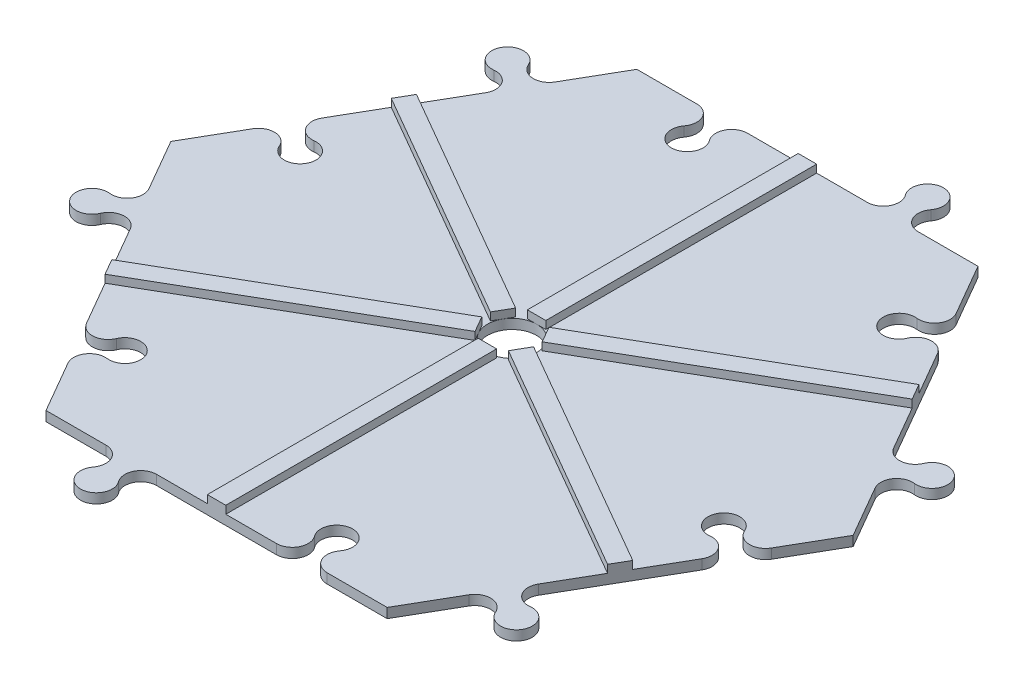
SolidWorks part; units mm, degrees
ref_plane "Front Plane" through (0, 0, 0) normal (0, 0, 1) x (1, 0, 0)
ref_plane "Top Plane" through (0, 0, 0) normal (0, 1, 0) x (1, 0, 0)
ref_plane "Right Plane" through (0, 0, 0) normal (1, 0, 0) x (0, 0, -1)
sketch "Sketch1" plane through (0, 0, 0) normal (0, 1, 0) x (1, 0, 0)
  line L10 (55.5, -96.1288) -> (111, 0)
  line L11 (111, 0) -> (55.5, 96.1288)
  line L12 (55.5, 96.1288) -> (-55.5, 96.1288)
  line L13 (-55.5, 96.1288) -> (-111, 0)
  line L14 (-111, 0) -> (-55.5, -96.1288)
  line L15 (-55.5, -96.1288) -> (55.5, -96.1288)
  circle A3 centre (0, 0) radius 96.1288 construction
  dimension "D1" = 111
extrude "Boss-Extrude1" add sketch "Sketch1" along normal blind 3.175 contours L14 L15 L10 L11 L12 L13
sketch "Sketch2" plane through (0, 0, 0) normal (0, 1, 0) x (1, 0, 0)
  line L0 (-19.495, 96.1288) -> (-36.005, 96.1288)
  line L1 (0, 0) -> (0, 96.1288) construction
  line L2 (0, 96.1288) -> (55.5, 96.1288) construction
  line L4 (27.75, 96.1288) -> (27.75, 118.9888) construction
  line L5 (19.495, 96.1288) -> (36.005, 96.1288)
  line L7 (55.5, 96.1288) -> (-55.5, 96.1288) construction
  arc A0 (-31.8775, 104.3838) -> (-27.75, 112.6388) centre (-27.75, 107.4794) cw construction
  arc A1 (-23.6225, 104.3838) -> (-27.75, 112.6388) centre (-27.75, 107.4794) ccw construction
  arc A2 (-19.495, 96.1288) -> (-23.6225, 104.3838) centre (-19.495, 101.2882) cw construction
  arc A3 (19.495, 96.1288) -> (23.6225, 104.3838) centre (19.495, 101.2882) ccw
  arc A4 (-36.005, 96.1288) -> (-31.8775, 104.3838) centre (-36.005, 101.2882) ccw construction
  arc A5 (23.6225, 104.3838) -> (27.75, 112.6388) centre (27.75, 107.4794) cw
  arc A7 (36.005, 96.1288) -> (31.8775, 104.3838) centre (36.005, 101.2882) cw
  arc A8 (31.8775, 104.3838) -> (27.75, 112.6388) centre (27.75, 107.4794) ccw
  arc A9 (-19.495, 96.1288) -> (-23.6225, 87.8738) centre (-19.495, 90.9694) ccw
  arc A10 (-23.6225, 87.8738) -> (-27.75, 79.6188) centre (-27.75, 84.7782) cw
  arc A11 (-31.8775, 87.8738) -> (-27.75, 79.6188) centre (-27.75, 84.7782) ccw
  arc A12 (-36.005, 96.1288) -> (-31.8775, 87.8738) centre (-36.005, 90.9694) cw
  dimension "D1" = 22.86
  dimension "D3" = 16.51
  dimension "D4" = 16.51
extrude "Boss-Extrude2" add sketch "Sketch2" along normal up to surface (3.175 mm away) contours A7 A8 A5 A3 L5 up to face at (0, 3.175, 0)
extrude "Cut-Extrude2" cut sketch "Sketch2<3>" along normal through all contours A11 A10 A9 L0 A12
sketch "Sketch2<3>" plane through (0, 0, 0) normal (0, 1, 0) x (1, 0, 0) same geometry as "Sketch2"
sketch "Sketch3" [suppressed] plane through (0, 0, 0) normal (0, 0, 1) x (1, 0, 0)
  line L0 (0, 0) -> (0, 25.4) construction
  dimension "D1" = 25.4
pattern_circular "CirPattern1" count 6 over 360 about axis through (0, 0, 0) along (0, 1, 0) of "Boss-Extrude2", "Cut-Extrude2" reverse direction yes
sketch "Sketch4" plane through (0, 3.175, 0) normal (0, 1, 0) x (1, 0, 0)
  circle A0 centre (0, 0) radius 8.001
  dimension "D1" = 16.002
extrude "Cut-Extrude3" cut sketch "Sketch4" against normal up to surface (3.175 mm away) up to face at (0, 0, 0)
sketch "Sketch5" plane through (0, 3.175, 0) normal (0, 1, 0) x (1, 0, 0)
  line L0 (-84.75, -45.4663) -> (-7.9236, -1.1106)
  line L1 (-81.75, -50.6625) -> (-4.9236, -6.3067)
  line L2 (-92.9975, -31.1812) -> (-73.5025, -64.9476) construction
  line L3 (-83.25, -48.0644) -> (-6.9291, -4.0005) construction
  line L4 (-7.9236, -1.1106) -> (-4.9236, -6.3067)
  line L5 (-92.9975, -31.1812) -> (-73.5025, -64.9476) construction
  line L6 (-84.75, -45.4663) -> (-81.75, -50.6625)
  line L7 (-5.4291, -6.5986) -> (-8.4291, -1.4024)
  circle A0 centre (0, 0) radius 8.001 construction
  arc A1 (-7.9236, -1.1106) -> (-4.9236, -6.3067) centre (0, 0) ccw
  dimension "D1" = 6
extrude "Boss-Extrude3" add sketch "Sketch5" along normal blind 2.54 contours L6 L3 L7 L0 | L3 L6 L1 L7 region at (-45.8395, 3.175, 24.7334) region at (-44.3395, 3.175, 27.3315)
pattern_circular "CirPattern2" count 6 over 360 about axis through (0, -22.6302, 0) along (0, 1, 0) of "Boss-Extrude3"
sketch "Sketch6" plane through (0, 3.175, 0) normal (0, 1, 0) x (1, 0, 0)
  line L0 (-81.75, 50.6625) -> (-5.4291, 6.5986) construction
  line L1 (-5.4291, 6.5986) -> (-6.9291, 4.0005) construction
  line L2 (0, 8.001) -> (-3, 8.001) construction
  line L3 (-3, 8.001) -> (-3, 96.1288) construction
  line L4 (-3, 96.1288) -> (-19.495, 96.1288) construction
  line L5 (-36.005, 96.1288) -> (-55.5, 96.1288) construction
  line L6 (-55.5, 96.1288) -> (-65.2475, 79.2457) construction
  line L7 (-73.5025, 64.9476) -> (-81.75, 50.6625) construction
  line L8 (-6.9291, 4.0005) -> (-8.4291, 1.4024) construction
  line L9 (-8.4291, 1.4024) -> (-84.75, 45.4663) construction
  line L10 (-84.75, 45.4663) -> (-92.9975, 31.1812) construction
  line L11 (-101.2525, 16.8832) -> (-111, 0) construction
  line L12 (-111, 0) -> (-101.2525, -16.8832) construction
  line L13 (-92.9975, -31.1812) -> (-84.75, -45.4663) construction
  line L14 (-84.75, -45.4663) -> (-8.4291, -1.4024) construction
  line L15 (-8.4291, -1.4024) -> (-6.9291, -4.0005) construction
  line L16 (-3, -96.1288) -> (-3, -8.001) construction
  line L17 (-3, -8.001) -> (0, -8.001) construction
  line L18 (-6.9291, -4.0005) -> (-5.4291, -6.5986) construction
  line L19 (-5.4291, -6.5986) -> (-81.75, -50.6625) construction
  line L20 (-81.75, -50.6625) -> (-73.5025, -64.9476) construction
  line L21 (-65.2475, -79.2457) -> (-55.5, -96.1288) construction
  line L22 (-55.5, -96.1288) -> (-36.005, -96.1288) construction
  line L23 (-19.495, -96.1288) -> (-3, -96.1288) construction
  line L24 (81.75, -50.6625) -> (5.4291, -6.5986) construction
  line L25 (5.4291, -6.5986) -> (6.9291, -4.0005) construction
  line L26 (0, -8.001) -> (3, -8.001) construction
  line L27 (3, -8.001) -> (3, -96.1288) construction
  line L28 (3, -96.1288) -> (19.495, -96.1288) construction
  line L29 (36.005, -96.1288) -> (55.5, -96.1288) construction
  line L30 (55.5, -96.1288) -> (65.2475, -79.2457) construction
  line L31 (73.5025, -64.9476) -> (81.75, -50.6625) construction
  line L32 (84.75, 45.4663) -> (8.4291, 1.4024) construction
  line L33 (8.4291, 1.4024) -> (6.9291, 4.0005) construction
  line L34 (6.9291, -4.0005) -> (8.4291, -1.4024) construction
  line L35 (8.4291, -1.4024) -> (84.75, -45.4663) construction
  line L36 (84.75, -45.4663) -> (92.9975, -31.1812) construction
  line L37 (101.2525, -16.8832) -> (111, 0) construction
  line L38 (111, 0) -> (101.2525, 16.8832) construction
  line L39 (92.9975, 31.1812) -> (84.75, 45.4663) construction
  line L40 (3, 96.1288) -> (3, 8.001) construction
  line L41 (3, 8.001) -> (0, 8.001) construction
  line L42 (6.9291, 4.0005) -> (5.4291, 6.5986) construction
  line L43 (5.4291, 6.5986) -> (81.75, 50.6625) construction
  line L44 (81.75, 50.6625) -> (73.5025, 64.9476) construction
  line L45 (65.2475, 79.2457) -> (55.5, 96.1288) construction
  line L46 (55.5, 96.1288) -> (36.005, 96.1288) construction
  line L47 (19.495, 96.1288) -> (3, 96.1288) construction
  line L48 (-81.75, 50.6625) -> (-5.4291, 6.5986)
  line L49 (-5.4291, 6.5986) -> (-6.9291, 4.0005)
  line L50 (0, 8.001) -> (-3, 8.001)
  line L51 (-3, 8.001) -> (-3, 96.1288)
  line L52 (-3, 96.1288) -> (-19.495, 96.1288)
  line L53 (-36.005, 96.1288) -> (-55.5, 96.1288)
  line L54 (-55.5, 96.1288) -> (-65.2475, 79.2457)
  line L55 (-73.5025, 64.9476) -> (-81.75, 50.6625)
  line L56 (-6.9291, 4.0005) -> (-8.4291, 1.4024)
  line L57 (-8.4291, 1.4024) -> (-84.75, 45.4663)
  line L58 (-84.75, 45.4663) -> (-92.9975, 31.1812)
  line L59 (-101.2525, 16.8832) -> (-111, 0)
  line L60 (-111, 0) -> (-101.2525, -16.8832)
  line L61 (-92.9975, -31.1812) -> (-84.75, -45.4663)
  line L62 (-84.75, -45.4663) -> (-8.4291, -1.4024)
  line L63 (-8.4291, -1.4024) -> (-6.9291, -4.0005)
  line L64 (-3, -96.1288) -> (-3, -8.001)
  line L65 (-3, -8.001) -> (0, -8.001)
  line L66 (-6.9291, -4.0005) -> (-5.4291, -6.5986)
  line L67 (-5.4291, -6.5986) -> (-81.75, -50.6625)
  line L68 (-81.75, -50.6625) -> (-73.5025, -64.9476)
  line L69 (-65.2475, -79.2457) -> (-55.5, -96.1288)
  line L70 (-55.5, -96.1288) -> (-36.005, -96.1288)
  line L71 (-19.495, -96.1288) -> (-3, -96.1288)
  line L72 (81.75, -50.6625) -> (5.4291, -6.5986)
  line L73 (5.4291, -6.5986) -> (6.9291, -4.0005)
  line L74 (0, -8.001) -> (3, -8.001)
  line L75 (3, -8.001) -> (3, -96.1288)
  line L76 (3, -96.1288) -> (19.495, -96.1288)
  line L77 (36.005, -96.1288) -> (55.5, -96.1288)
  line L78 (55.5, -96.1288) -> (65.2475, -79.2457)
  line L79 (73.5025, -64.9476) -> (81.75, -50.6625)
  line L80 (84.75, 45.4663) -> (8.4291, 1.4024)
  line L81 (8.4291, 1.4024) -> (6.9291, 4.0005)
  line L82 (6.9291, -4.0005) -> (8.4291, -1.4024)
  line L83 (8.4291, -1.4024) -> (84.75, -45.4663)
  line L84 (84.75, -45.4663) -> (92.9975, -31.1812)
  line L85 (101.2525, -16.8832) -> (111, 0)
  line L86 (111, 0) -> (101.2525, 16.8832)
  line L87 (92.9975, 31.1812) -> (84.75, 45.4663)
  line L88 (3, 96.1288) -> (3, 8.001)
  line L89 (3, 8.001) -> (0, 8.001)
  line L90 (6.9291, 4.0005) -> (5.4291, 6.5986)
  line L91 (5.4291, 6.5986) -> (81.75, 50.6625)
  line L92 (81.75, 50.6625) -> (73.5025, 64.9476)
  line L93 (65.2475, 79.2457) -> (55.5, 96.1288)
  line L94 (55.5, 96.1288) -> (36.005, 96.1288)
  line L95 (19.495, 96.1288) -> (3, 96.1288)
  arc A1 (-19.495, 96.1288) -> (-23.6225, 87.8738) centre (-19.495, 90.9694) ccw construction
  arc A2 (-31.8775, 87.8738) -> (-23.6225, 87.8738) centre (-27.75, 84.7782) ccw construction
  arc A3 (-31.8775, 87.8738) -> (-36.005, 96.1288) centre (-36.005, 90.9694) ccw construction
  arc A4 (-74.4603, 79.7986) -> (-65.2475, 79.2457) centre (-69.7156, 81.8253) ccw construction
  arc A5 (-74.4603, 79.7986) -> (-78.5878, 72.6496) centre (-79.2049, 77.7719) ccw construction
  arc A6 (-73.5025, 64.9476) -> (-78.5878, 72.6496) centre (-77.9706, 67.5273) ccw construction
  arc A7 (-92.9975, 31.1812) -> (-87.9122, 23.4792) centre (-88.5294, 28.6016) ccw construction
  arc A8 (-92.0397, 16.3302) -> (-87.9122, 23.4792) centre (-87.2951, 18.3569) ccw construction
  arc A9 (-92.0397, 16.3302) -> (-101.2525, 16.8832) centre (-96.7844, 14.3035) ccw construction
  arc A10 (-106.3378, -24.5852) -> (-101.2525, -16.8832) centre (-105.7206, -19.4629) ccw construction
  arc A11 (-106.3378, -24.5852) -> (-102.2103, -31.7342) centre (-106.9549, -29.7075) ccw construction
  arc A12 (-92.9975, -31.1812) -> (-102.2103, -31.7342) centre (-97.4656, -33.7609) ccw construction
  arc A15 (-73.5025, -64.9476) -> (-64.2897, -64.3946) centre (-69.0344, -62.3679) ccw construction
  arc A16 (-60.1622, -71.5436) -> (-64.2897, -64.3946) centre (-59.5451, -66.4213) ccw construction
  arc A17 (-60.1622, -71.5436) -> (-65.2475, -79.2457) centre (-60.7794, -76.666) ccw construction
  arc A18 (-31.8775, -104.3838) -> (-36.005, -96.1288) centre (-36.005, -101.2882) ccw construction
  arc A19 (-31.8775, -104.3838) -> (-23.6225, -104.3838) centre (-27.75, -107.4794) ccw construction
  arc A20 (-19.495, -96.1288) -> (-23.6225, -104.3838) centre (-19.495, -101.2882) ccw construction
  arc A22 (19.495, -96.1288) -> (23.6225, -87.8738) centre (19.495, -90.9694) ccw construction
  arc A23 (31.8775, -87.8738) -> (23.6225, -87.8738) centre (27.75, -84.7782) ccw construction
  arc A24 (31.8775, -87.8738) -> (36.005, -96.1288) centre (36.005, -90.9694) ccw construction
  arc A25 (74.4603, -79.7986) -> (65.2475, -79.2457) centre (69.7156, -81.8253) ccw construction
  arc A26 (74.4603, -79.7986) -> (78.5878, -72.6496) centre (79.2049, -77.7719) ccw construction
  arc A27 (73.5025, -64.9476) -> (78.5878, -72.6496) centre (77.9706, -67.5273) ccw construction
  arc A29 (92.9975, -31.1812) -> (87.9122, -23.4792) centre (88.5294, -28.6016) ccw construction
  arc A30 (92.0397, -16.3302) -> (87.9122, -23.4792) centre (87.2951, -18.3569) ccw construction
  arc A31 (92.0397, -16.3302) -> (101.2525, -16.8832) centre (96.7844, -14.3035) ccw construction
  arc A32 (106.3378, 24.5852) -> (101.2525, 16.8832) centre (105.7206, 19.4629) ccw construction
  arc A33 (106.3378, 24.5852) -> (102.2103, 31.7342) centre (106.9549, 29.7075) ccw construction
  arc A34 (92.9975, 31.1812) -> (102.2103, 31.7342) centre (97.4656, 33.7609) ccw construction
  arc A36 (73.5025, 64.9476) -> (64.2897, 64.3946) centre (69.0344, 62.3679) ccw construction
  arc A37 (60.1622, 71.5436) -> (64.2897, 64.3946) centre (59.5451, 66.4213) ccw construction
  arc A38 (60.1622, 71.5436) -> (65.2475, 79.2457) centre (60.7794, 76.666) ccw construction
  arc A39 (31.8775, 104.3838) -> (36.005, 96.1288) centre (36.005, 101.2882) ccw construction
  arc A40 (31.8775, 104.3838) -> (23.6225, 104.3838) centre (27.75, 107.4794) ccw construction
  arc A41 (19.495, 96.1288) -> (23.6225, 104.3838) centre (19.495, 101.2882) ccw construction
  arc A43 (-19.495, 96.1288) -> (-23.6225, 87.8738) centre (-19.495, 90.9694) ccw
  arc A44 (-31.8775, 87.8738) -> (-23.6225, 87.8738) centre (-27.75, 84.7782) ccw
  arc A45 (-31.8775, 87.8738) -> (-36.005, 96.1288) centre (-36.005, 90.9694) ccw
  arc A46 (-74.4603, 79.7986) -> (-65.2475, 79.2457) centre (-69.7156, 81.8253) ccw
  arc A47 (-74.4603, 79.7986) -> (-78.5878, 72.6496) centre (-79.2049, 77.7719) ccw
  arc A48 (-73.5025, 64.9476) -> (-78.5878, 72.6496) centre (-77.9706, 67.5273) ccw
  arc A49 (-92.9975, 31.1812) -> (-87.9122, 23.4792) centre (-88.5294, 28.6016) ccw
  arc A50 (-92.0397, 16.3302) -> (-87.9122, 23.4792) centre (-87.2951, 18.3569) ccw
  arc A51 (-92.0397, 16.3302) -> (-101.2525, 16.8832) centre (-96.7844, 14.3035) ccw
  arc A52 (-106.3378, -24.5852) -> (-101.2525, -16.8832) centre (-105.7206, -19.4629) ccw
  arc A53 (-106.3378, -24.5852) -> (-102.2103, -31.7342) centre (-106.9549, -29.7075) ccw
  arc A54 (-92.9975, -31.1812) -> (-102.2103, -31.7342) centre (-97.4656, -33.7609) ccw
  arc A57 (-73.5025, -64.9476) -> (-64.2897, -64.3946) centre (-69.0344, -62.3679) ccw
  arc A58 (-60.1622, -71.5436) -> (-64.2897, -64.3946) centre (-59.5451, -66.4213) ccw
  arc A59 (-60.1622, -71.5436) -> (-65.2475, -79.2457) centre (-60.7794, -76.666) ccw
  arc A60 (-31.8775, -104.3838) -> (-36.005, -96.1288) centre (-36.005, -101.2882) ccw
  arc A61 (-31.8775, -104.3838) -> (-23.6225, -104.3838) centre (-27.75, -107.4794) ccw
  arc A62 (-19.495, -96.1288) -> (-23.6225, -104.3838) centre (-19.495, -101.2882) ccw
  arc A64 (19.495, -96.1288) -> (23.6225, -87.8738) centre (19.495, -90.9694) ccw
  arc A65 (31.8775, -87.8738) -> (23.6225, -87.8738) centre (27.75, -84.7782) ccw
  arc A66 (31.8775, -87.8738) -> (36.005, -96.1288) centre (36.005, -90.9694) ccw
  arc A67 (74.4603, -79.7986) -> (65.2475, -79.2457) centre (69.7156, -81.8253) ccw
  arc A68 (74.4603, -79.7986) -> (78.5878, -72.6496) centre (79.2049, -77.7719) ccw
  arc A69 (73.5025, -64.9476) -> (78.5878, -72.6496) centre (77.9706, -67.5273) ccw
  arc A71 (92.9975, -31.1812) -> (87.9122, -23.4792) centre (88.5294, -28.6016) ccw
  arc A72 (92.0397, -16.3302) -> (87.9122, -23.4792) centre (87.2951, -18.3569) ccw
  arc A73 (92.0397, -16.3302) -> (101.2525, -16.8832) centre (96.7844, -14.3035) ccw
  arc A74 (106.3378, 24.5852) -> (101.2525, 16.8832) centre (105.7206, 19.4629) ccw
  arc A75 (106.3378, 24.5852) -> (102.2103, 31.7342) centre (106.9549, 29.7075) ccw
  arc A76 (92.9975, 31.1812) -> (102.2103, 31.7342) centre (97.4656, 33.7609) ccw
  arc A78 (73.5025, 64.9476) -> (64.2897, 64.3946) centre (69.0344, 62.3679) ccw
  arc A79 (60.1622, 71.5436) -> (64.2897, 64.3946) centre (59.5451, 66.4213) ccw
  arc A80 (60.1622, 71.5436) -> (65.2475, 79.2457) centre (60.7794, 76.666) ccw
  arc A81 (31.8775, 104.3838) -> (36.005, 96.1288) centre (36.005, 101.2882) ccw
  arc A82 (31.8775, 104.3838) -> (23.6225, 104.3838) centre (27.75, 107.4794) ccw
  arc A83 (19.495, 96.1288) -> (23.6225, 104.3838) centre (19.495, 101.2882) ccw
